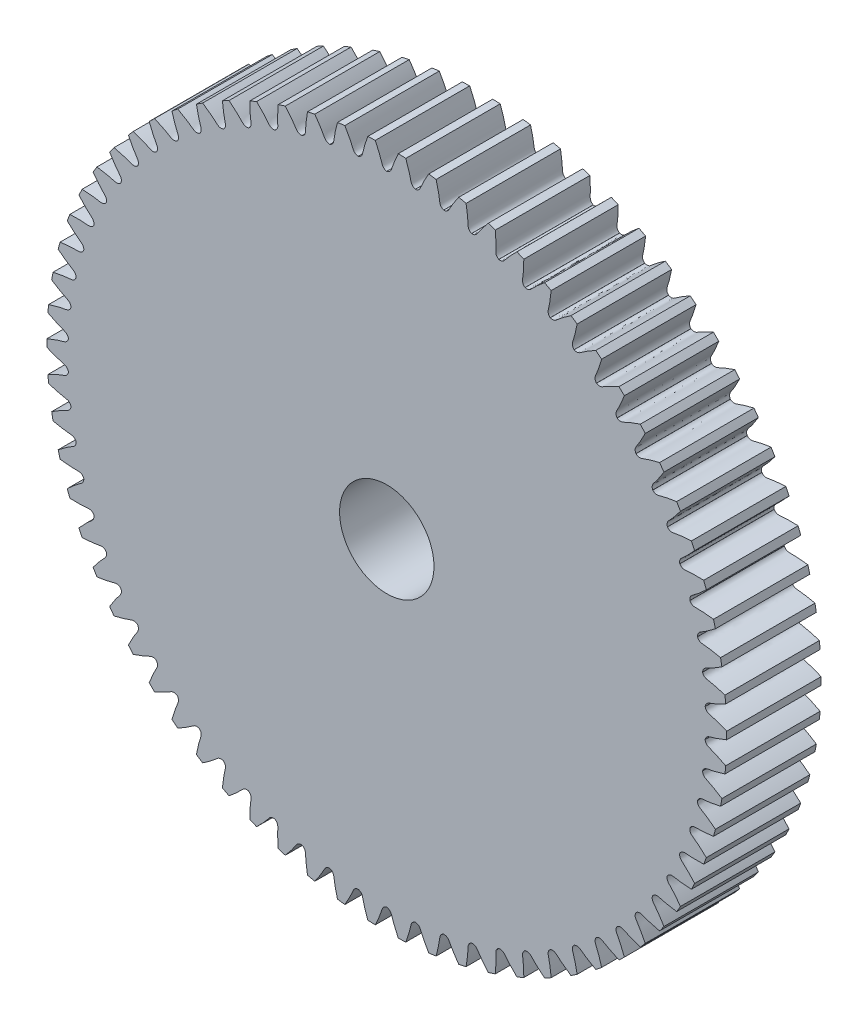
SolidWorks part; units mm, degrees
ref_plane "前视基准面" through (0, 0, 0) normal (0, 0, 1) x (1, 0, 0)
ref_plane "上视基准面" through (0, 0, 0) normal (0, 1, 0) x (1, 0, 0)
ref_plane "右视基准面" through (0, 0, 0) normal (1, 0, 0) x (0, 0, -1)
other "Configuration Table"
sketch "草图1" plane through (0, 0, 0) normal (0, 0, 1) x (1, 0, 0)
  circle A0 centre (0, 0) radius 108
extrude "凸台-拉伸1" add sketch "草图1" along normal blind 30
ref_axis "基准轴1" through (0, 0, 30) along (0, 0, -1)
sketch "草图2" plane through (0, 0, 0) normal (0, 0, 1) x (1, 0, 0)
  line L0 (0, 0) -> (0, 108) construction
  circle A0 centre (0, 0) radius 108 construction
  arc A1 (0.01, 101.2493) -> (-0.01, 101.2493) centre (0, 0) ccw
  arc A2 (14.058, 122.5587) -> (-14.058, 122.5587) centre (0, 0) ccw
  spline S0 degree 3 poles (0.01, 101.2493) (1.2867, 101.5053) (1.5171, 102.6356) (1.9603, 103.9101) (2.1886, 104.5422) (2.445, 105.2057) (2.7292, 105.9007) (3.043, 106.6261) (3.3876, 107.3809) (3.7643, 108.1643) (4.1744, 108.9752) (4.6191, 109.8126) (5.0997, 110.6754) (5.6173, 111.5626) (6.1732, 112.4729) (6.7684, 113.4051) (7.404, 114.3582) (8.081, 115.3307) (8.8006, 116.3214) (9.5637, 117.329) (10.3712, 118.3521) (11.224, 119.3894) (12.44, 120.8093) (13.3973, 121.8608) (14.058, 122.5587) knots 0 0 0 0 0.106638 0.13117 0.157233 0.184827 0.213952 0.244607 0.276794 0.310512 0.345761 0.382541 0.420852 0.460693 0.502066 0.54497 0.589405 0.635371 0.682868 0.731896 0.782455 0.834544 0.888165 1 1 1 1
  spline S1 degree 3 poles (-0.01, 101.2493) (-1.2867, 101.5053) (-1.5171, 102.6356) (-1.9603, 103.9101) (-2.1886, 104.5422) (-2.445, 105.2057) (-2.7292, 105.9007) (-3.043, 106.6261) (-3.3876, 107.3809) (-3.7643, 108.1643) (-4.1744, 108.9752) (-4.6191, 109.8126) (-5.0997, 110.6754) (-5.6173, 111.5626) (-6.1732, 112.4729) (-6.7684, 113.4051) (-7.404, 114.3582) (-8.081, 115.3307) (-8.8006, 116.3214) (-9.5637, 117.329) (-10.3712, 118.3521) (-11.224, 119.3894) (-12.44, 120.8093) (-13.3973, 121.8608) (-14.058, 122.5587) knots 0 0 0 0 0.106638 0.13117 0.157233 0.184827 0.213952 0.244607 0.276794 0.310512 0.345761 0.382541 0.420852 0.460693 0.502066 0.54497 0.589405 0.635371 0.682868 0.731896 0.782455 0.834544 0.888165 1 1 1 1
extrude "切除-拉伸1" cut sketch "草图2" along normal through all
pattern_circular "阵列(圆周)1" count 70 every 5.143 about axis through (0, 0, 30) along (0, 0, -1) of "切除-拉伸1"
sketch "草图3" plane through (0, 0, 0) normal (0, 0, 1) x (1, 0, 0)
  circle A0 centre (0, 0) radius 105 construction
  dimension "Dn" = 210
sketch "草图4" plane through (0, 0, 30) normal (0, 0, 1) x (1, 0, 0)
  circle A0 centre (0, 0) radius 15
  dimension "D1" = 30
extrude "切除-拉伸2" cut sketch "草图4" against normal blind 300
ref_plane "基准面1" through (0, 0, 15) normal (0, 0, 1) x (1, 0, 0)
